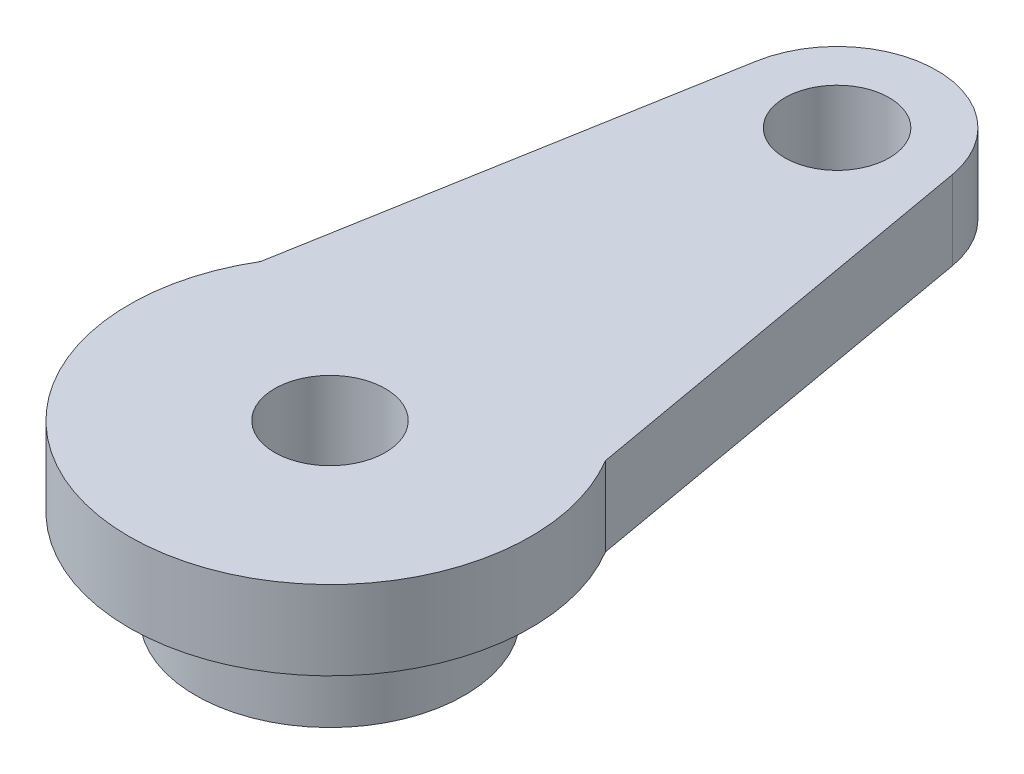
SolidWorks part; units mm, degrees
material "PC High Viscosity"
ref_plane "Front Plane" through (0, 0, 0) normal (0, 0, 1) x (1, 0, 0)
ref_plane "Top Plane" through (0, 0, 0) normal (0, 1, 0) x (1, 0, 0)
ref_plane "Right Plane" through (0, 0, 0) normal (1, 0, 0) x (0, 0, -1)
sketch "BaseS" plane through (0, 0, 0) normal (0, 1, 0) x (1, 0, 0)
  circle A0 centre (0, 0) radius 6.35
  dimension "D1" = 12.7
extrude "BASE" add sketch "BaseS" along normal blind 5.4
sketch "TopBoreS" plane through (0, 5.4, 0) normal (0, 1, 0) x (1, 0, 0)
  circle A0 centre (0, 0) radius 1.75
  dimension "D1" = 3.5
extrude "TOP BORE" cut sketch "TopBoreS" against normal through all
sketch "HornHalfS" plane through (0, 5.4, 0) normal (0, 1, 0) x (1, 0, 0)
  line L0 (0, 0) -> (0, 16.03) construction
  line L1 (-3.1021, 16.577) -> (-5.4507, 3.2577)
  line L2 (0, 19.18) -> (0, 16.03) construction
  line L3 (3.1021, 16.577) -> (5.4507, 3.2577)
  arc A0 (3.1021, 16.577) -> (-3.1021, 16.577) centre (0, 16.03) ccw
  arc A1 (5.4507, 3.2577) -> (-5.4507, 3.2577) centre (0, 0) ccw
  circle A2 centre (0, 0) radius 6.35 construction
  dimension "D1" = 6.3
  dimension "D2" = 19.18
  dimension "D3" = 10
  dimension "D4" = 10.9014
extrude "HORN HALF" add sketch "HornHalfS" against normal blind 2.5
sketch "HornAttachS" plane through (0, 5.4, 0) normal (0, 1, 0) x (1, 0, 0)
  circle A0 centre (0, 16.03) radius 1.65
  dimension "D1" = 3.3
extrude "HORN ATTACH" cut sketch "HornAttachS" against normal through all
sketch "HA LP RS" plane through (0, 0, 0) normal (0, 1, 0) x (1, 0, 0)
  line L0 (0, 0) -> (0, 16.03) construction
sketch "ToothS" plane through (0, 0, 0) normal (0, -1, 0) x (1, 0, 0)
  line L0 (0, -2.9) -> (0.2629, -2.5867)
  line L1 (0, -2.9) -> (-0.2629, -2.5867)
  line L2 (0, -2.6) -> (0, -2.9) construction
  line L3 (0, 0) -> (0, -2.6) construction
  arc A0 (-0.2629, -2.5867) -> (0.2629, -2.5867) centre (0, 0) ccw
  dimension "D1" = 5.2
  dimension "D2" = 80
  dimension "D3" = 0.3
extrude "TOOTH" [suppressed] cut sketch "ToothS" against normal blind 3
pattern_circular "TOOTH CP" [suppressed] count 26 over 360 of bodies 107
sketch "BottomBoreS" [suppressed] plane through (0, 0, 0) normal (0, -1, 0) x (-1, 0, 0)
  circle A0 centre (0, 0) radius 2.6
  arc A1 (0.2629, 2.5867) -> (-0.2629, 2.5867) centre (0, 0) ccw construction
extrude "BOTTOM BORE" [suppressed] cut sketch "BottomBoreS" against normal up to surface (3 mm away)
sketch "HoldingShaftS" plane through (0, 0, 0) normal (0, -1, 0) x (1, 0, 0)
  circle A0 centre (0, 0) radius 6.35 construction
  circle A1 centre (0, 0) radius 6.35
  circle A2 centre (0, 0) radius 4.25
  dimension "D1" = 2.1
  dimension "D2" = 8.5
extrude "HOLDING SHAFT" cut sketch "HoldingShaftS" against normal up to surface (2.9 mm away) up to face at (0, 2.9, -14.38)
sketch "RibS" plane through (0, 0, 0) normal (0, 0, 1) x (1, 0, 0)
  line L0 (4.21, 1) -> (5.8043, 2.9)
  line L1 (5.8043, 2.9) -> (4.21, 2.9)
  line L2 (4.21, 1) -> (4.16, 1)
  line L3 (4.16, 1) -> (4.16, 2.9)
  line L4 (4.21, 1) -> (4.21, 2.9) construction
  line L5 (4.16, 2.9) -> (4.21, 2.9)
  line L6 (-4.25, 2.9) -> (4.25, 2.9) construction
  line L7 (4.21, 2.9) -> (4.25, 2.9) construction
  line L8 (4.25, 0) -> (4.25, 2.9) construction
  dimension "D1" = 1.9
  dimension "D2" = 0.05
  dimension "D3" = 40
  dimension "D4" = 0.09
extrude "RIB" [suppressed] add sketch "RibS" along normal mid plane 1
pattern_circular "RIB CP" [suppressed] count 4 over 360 of bodies 111
sketch "Sketch1" plane through (0, 5.4, 0) normal (0, 1, 0) x (1, 0, 0)
  circle A0 centre (0, 0) radius 2.875
  dimension "D1" = 5.75
extrude "Cut-Extrude1" [suppressed] cut sketch "Sketch1" against normal blind 1
ref_point "Point1"
ref_point "Point2" [suppressed]
ref_axis "Axis1" [suppressed] through (0, 5.4, 0) along (0, 0, -1)
sketch "Sketch3" plane through (0, 0, 0) normal (0, -1, 0) x (1, 0, 0)
  circle A0 centre (0, 0) radius 3.025
  dimension "D1" = 6.05
extrude "Cut-Extrude2" cut sketch "Sketch3" against normal up to surface (2.9 mm away) up to face at (0, 2.9, -14.38)
